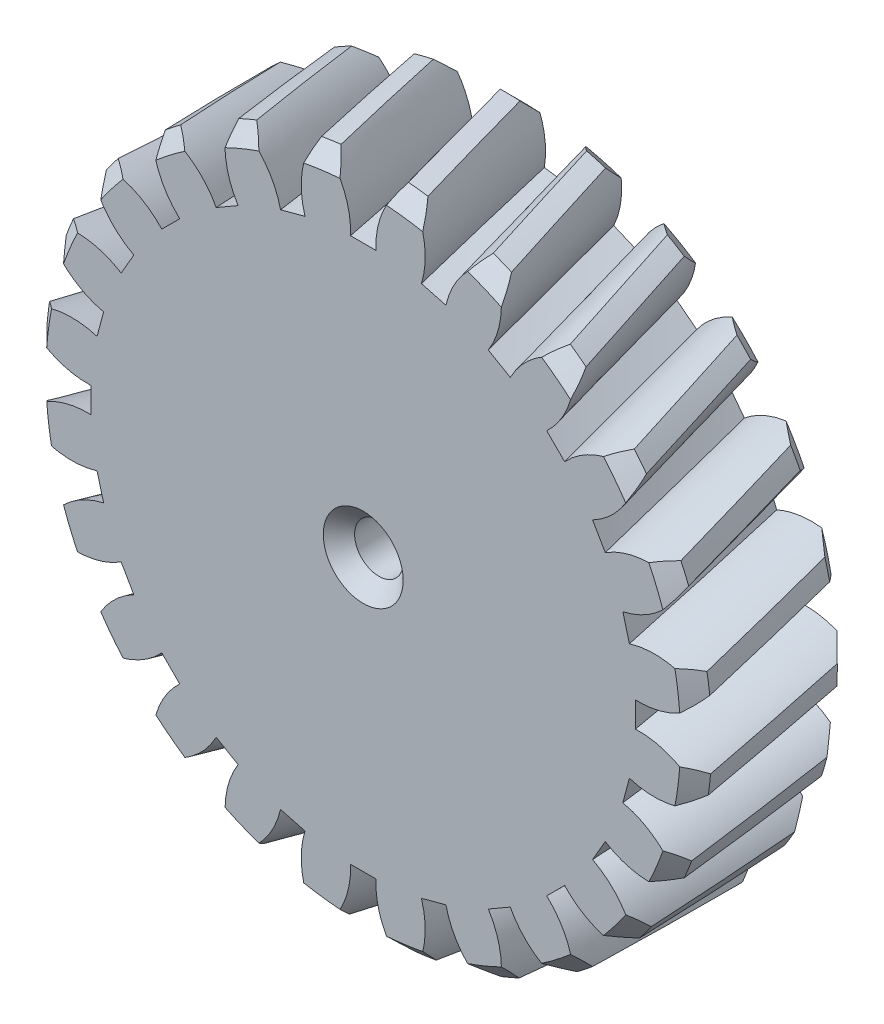
SolidWorks part; units mm, degrees
ref_plane "Front Plane" through (0, 0, 0) normal (1, 0, 0) x (0, 1, 0)
ref_plane "Top Plane" through (0, 0, 0) normal (0, 0, 1) x (0, 1, 0)
ref_plane "Right Plane" through (0, 0, 0) normal (0, 1, 0) x (-1, 0, 0)
sketch "Sketch5" plane through (0, 0, 0) normal (0, 0, 1) x (0, 1, 0)
  circle A0 centre (0, 0) radius 21.25
  circle A1 centre (0, 0) radius 1.55
  dimension "D1" = 42.5
  dimension "D2" = 3.1
extrude "Boss-Extrude1" add sketch "Sketch5" along normal blind 10
sketch "Sketch3" plane through (0, 0, 0) normal (0, 0, 1) x (0, 1, 0)
  line L0 (-4.75, 0) -> (-4.3361, 2.5035) construction
  line L1 (0, 0) -> (0, 4.3731) construction
  line L2 (4.75, 0) -> (4.3361, 2.5035) construction
  line L3 (-0.9247, 4.6591) -> (0, 5.0069) construction
  line L4 (2.375, -4.1136) -> (4.3361, -2.5035) construction
  line L5 (2.375, 4.1136) -> (4.3361, 2.5035) construction
  line L6 (-2.375, -4.1136) -> (0, -5.0069) construction
  line L7 (4.75, 0) -> (4.3361, -2.5035) construction
  line L8 (-4.75, 0) -> (-4.3361, -2.5035) construction
  line L9 (2.375, -4.1136) -> (0, -5.0069) construction
  line L10 (-3.5726, 3.1304) -> (-4.3361, 2.5035) construction
  line L11 (-2.375, -4.1136) -> (-4.3361, -2.5035) construction
  line L12 (2.375, 4.1136) -> (0, 5.0069) construction
  line L13 (-3.6926, 6.3958) -> (-2.4665, 13.8125)
  line L14 (-3.6926, 6.3958) -> (-10.7287, 9.0423)
  line L15 (3.6926, 6.3958) -> (10.7287, 9.0423)
  line L16 (3.6926, 6.3958) -> (2.4665, 13.8125)
  line L17 (7.3853, 0) -> (13.1953, -4.7702)
  line L18 (7.3853, 0) -> (13.1953, 4.7702)
  line L19 (3.6926, -6.3958) -> (2.4665, -13.8125)
  line L20 (3.6926, -6.3958) -> (10.7287, -9.0423)
  line L21 (-3.6926, -6.3958) -> (-10.7287, -9.0423)
  line L22 (-3.6926, -6.3958) -> (-2.4665, -13.8125)
  line L23 (-7.3853, 0) -> (-13.1953, 4.7702)
  line L24 (-7.3853, 0) -> (-13.1953, -4.7702)
  arc A2 (-3.5726, 3.1304) -> (-0.9247, 4.6591) centre (0, 0) ccw construction
  arc A3 (-2.4665, 13.8125) -> (2.4665, 13.8125) centre (0, 13.4048) cw
  arc A4 (10.7287, 9.0423) -> (13.1953, 4.7702) centre (11.6089, 6.7024) cw
  arc A5 (13.1953, -4.7702) -> (10.7287, -9.0423) centre (11.6089, -6.7024) cw
  arc A6 (2.4665, -13.8125) -> (-2.4665, -13.8125) centre (0, -13.4048) cw
  arc A7 (-10.7287, -9.0423) -> (-13.1953, -4.7702) centre (-11.6089, -6.7024) cw
  arc A8 (-13.1953, 4.7702) -> (-10.7287, 9.0423) centre (-11.6089, 6.7024) cw
  dimension "D1" = 9.5
  dimension "D2" = 14
  dimension "D3" = 2.5
  dimension "D4" = 6
extrude "Cut-Extrude1" cut sketch "Sketch3" along normal blind 3
fillet "Fillet1" radius 1 18 edges at (-10.1042, -3.0796, 0) (-10.1042, 3.0796, 0) (-7.7191, 7.2107, 0) (-7.9524, 13.7739, 0) (-2.3851, 10.2903, 0) (2.3851, 10.2903, 0) (7.9524, 13.7739, 0) (7.7191, 7.2107, 0) (10.1042, 3.0796, 0) (15.9048, 0, 0) (10.1042, -3.0796, 0) (7.7191, -7.2107, 0) (7.9524, -13.7739, 0) (2.3851, -10.2903, 0) (-2.3851, -10.2903, 0) (-7.9524, -13.7739, 0) (-7.7191, -7.2107, 0) (-15.9048, 0, 0)
chamfer "Chamfer1" distance 1 angle 45 3 edges at (1.55, 0, 10) (21.25, 0, 10) (21.25, 0, 0)
sketch "Sketch9" plane through (0, 0, 10) normal (0, 0, 1) x (1, 0, 0)
  circle A0 centre (0, 0) radius 21.25 construction
  circle A1 centre (0, 0) radius 21.25
curve "Helix/Spiral1" pitch 500 height 20 radius 21.25 left hand yes centre (0, 0, 10) axis (0, 0, -1) start towards (-1, 0, 0)
sketch "Sketch10" plane through (0, 0, 10) normal (0, 0, 1) x (1, 0, 0)
  line L0 (0, 0) -> (31, 0) construction
  line L1 (17.368, 0.8085) -> (17.368, -0.8085)
  circle A0 centre (0, 0) radius 21.25 construction
  arc A1 (21.141, -2.15) -> (21.141, 2.15) centre (0, 0) ccw
  arc A2 (17.368, 0.8085) -> (21.141, 2.15) centre (17.578, 6.1944) ccw
  arc A3 (17.368, -0.8085) -> (21.141, -2.15) centre (17.578, -6.1944) cw
  point P9 (17.368, 0)
  dimension "D2" = 4.3
  dimension "D4" = 5.39
  dimension "D1" = 1.617
  dimension "D3" = 3.773
sweep "Cut-Sweep1" cut profiles "Sketch10" path "Helix/Spiral1" align with end faces yes
pattern_circular "CirPattern1" count 24 over 360 about axis through (0, 0, 10) along (0, 0, -1) of "Cut-Sweep1" reverse direction yes
